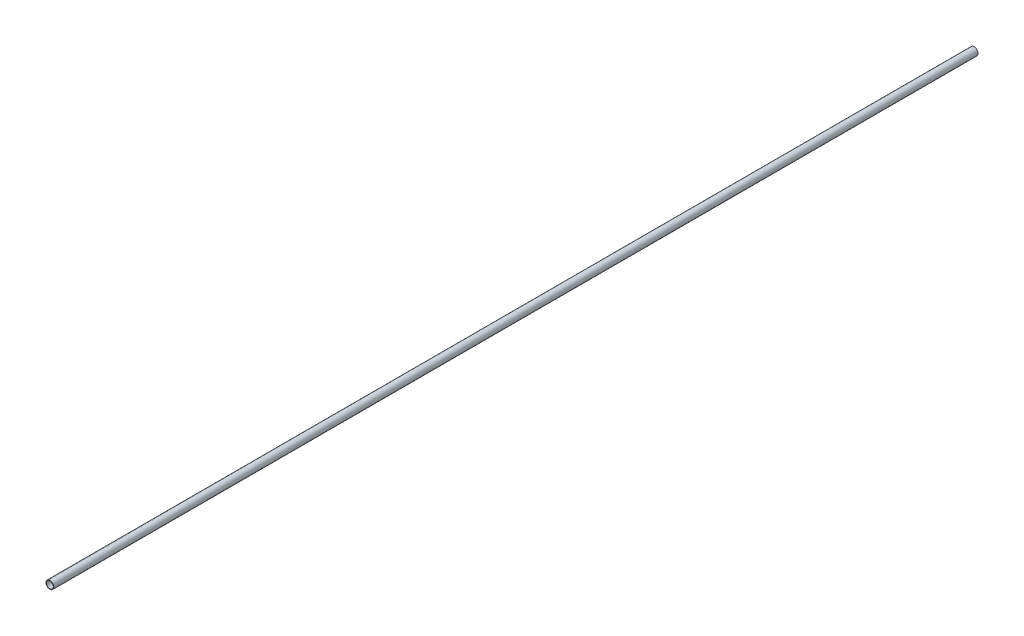
SolidWorks part; units mm, degrees
material "Thornel Mat VMA"
ref_plane "前视基准面" through (0, 0, 0) normal (0, 0, 1) x (1, 0, 0)
ref_plane "上视基准面" through (0, 0, 0) normal (0, 1, 0) x (1, 0, 0)
ref_plane "右视基准面" through (0, 0, 0) normal (1, 0, 0) x (0, 0, -1)
sketch "草图1" plane through (0, 0, 0) normal (0, 0, 1) x (1, 0, 0)
  circle A0 centre (0, 0) radius 4
  circle A1 centre (0, 0) radius 3.5
  dimension "D1" = 8
  dimension "D2" = 0.5
extrude "凸台-拉伸1" add sketch "草图1" along normal blind 474.25 and the other way blind 474.25
sketch "草图2" plane through (0, 0, 0) normal (0, 1, 0) x (1, 0, 0)
  line L0 (0, 0) -> (85.9285, 0) construction
